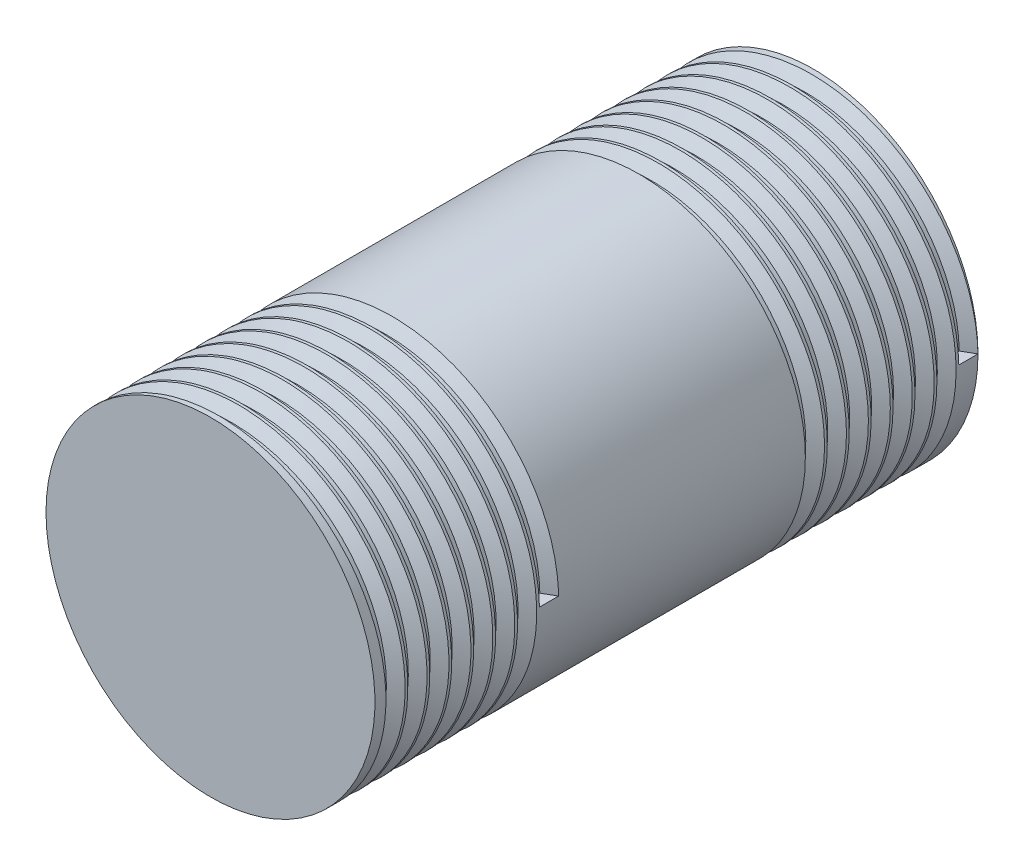
SolidWorks part; units mm, degrees
material "0.6010 (EN-GJL-100)"
ref_plane "Ön Düzlem" through (0, 0, 0) normal (0, 0, 1) x (1, 0, 0)
ref_plane "Üst Düzlem" through (0, 0, 0) normal (0, 1, 0) x (1, 0, 0)
ref_plane "Sağ Düzlem" through (0, 0, 0) normal (1, 0, 0) x (0, 0, -1)
sketch "Çizim1" plane through (0, 0, 0) normal (0, 0, 1) x (1, 0, 0)
  circle A0 centre (0, 0) radius 15
  dimension "D1" = 30
extrude "Yükseklik-Ekstrüzyon1" add sketch "Çizim1" along normal blind 55
thread "Diş1" pitch 2 method cut profile "Diş Profili1" start angle 0, offset 0, length 15, pitch 2, diameter 30
ref_plane "Düzlem1" through (-15, 0, 55) normal (0, -1, 0) x (-1, 0, 0)
sketch "Diş Profili1" plane through (-15, 0, 55) normal (0, -1, 0) x (-1, 0, 0)
  line L0 (0, 0) -> (0, 2) construction
  line L11 (0, 0) -> (0, 1.75)
  line L12 (0, 1.75) -> (-1.0825, 1.125)
  line L13 (-1.0825, 1.125) -> (-1.0825, 0.625)
  line L15 (-1.0825, 0.625) -> (0, 0)
  line L17 (-1.0825, 0.875) -> (0, 0.875) construction
  point P2 (0, 0)
  dimension "Pitch" = 2
  dimension "Profile_Angle" = 60
  dimension "Profile_Land" = 0.5
  dimension "Profile_Height" = 1.0825
thread "Diş2" pitch 2 method cut profile "Diş Profili2" start angle 0, offset 0, length 15, pitch 2, diameter 30
ref_plane "Düzlem2" through (15, 0, 0) normal (0, -1, 0) x (1, 0, 0)
sketch "Diş Profili2" plane through (15, 0, 0) normal (0, -1, 0) x (1, 0, 0)
  line L0 (0, 0) -> (0, 2) construction
  line L11 (0, 0) -> (0, 1.75)
  line L12 (0, 1.75) -> (-1.0825, 1.125)
  line L13 (-1.0825, 1.125) -> (-1.0825, 0.625)
  line L15 (-1.0825, 0.625) -> (0, 0)
  line L17 (-1.0825, 0.875) -> (0, 0.875) construction
  point P2 (0, 0)
  dimension "Pitch" = 2
  dimension "Profile_Angle" = 60
  dimension "Profile_Land" = 0.5
  dimension "Profile_Height" = 1.0825
